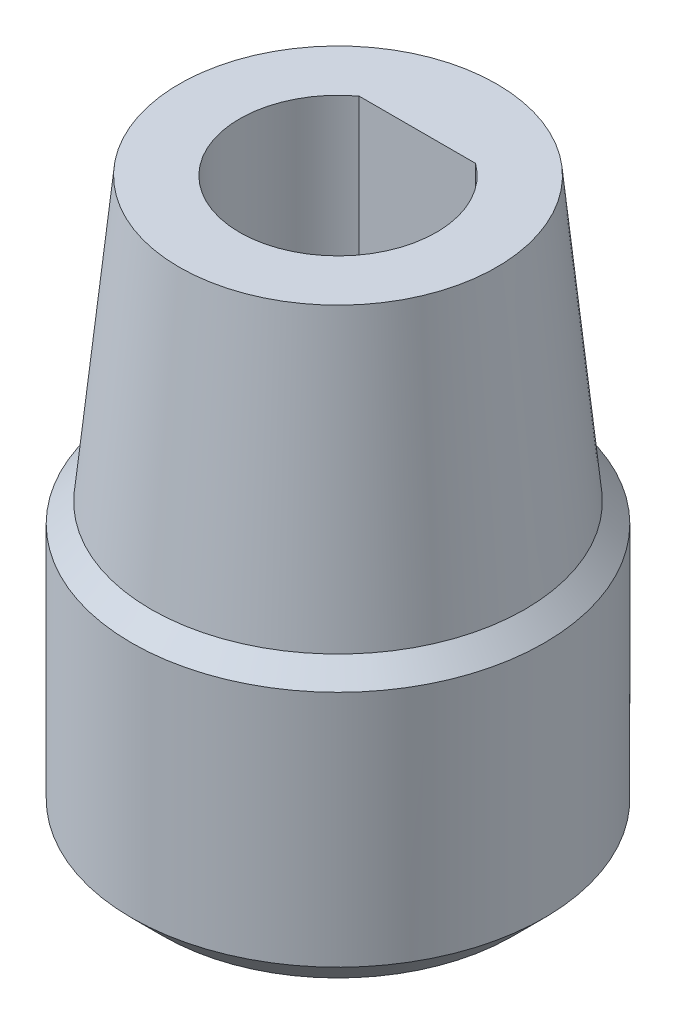
SolidWorks part; units mm, degrees
ref_plane "Front Plane" through (0, 0, 0) normal (0, 0, 1) x (1, 0, 0)
ref_plane "Top Plane" through (0, 0, 0) normal (0, 1, 0) x (1, 0, 0)
ref_plane "Right Plane" through (0, 0, 0) normal (1, 0, 0) x (0, 0, -1)
sketch "Sketch1" plane through (0, 0, 0) normal (0, 1, 0) x (1, 0, 0)
  line L0 (-1.833, 2.5) -> (1.833, 2.5)
  circle A0 centre (0, 0) radius 4.9
  circle A1 centre (0, 0) radius 3.1
  circle A2 centre (0, 0) radius 6
  circle A3 centre (0, 0) radius 6.5
  dimension "D1" = 9.8
  dimension "D2" = 6.2
  dimension "D4" = 12
  dimension "D5" = 13
  dimension "D3" = 2.5
extrude "Boss-Extrude1" add sketch "Sketch1" along normal blind 10 contours A2 A1 | L0 A1 | A2 A0 region at (0, 0, -2.7421) region at (-4.7614, 0, 0) region at (-5.8303, 0, 0)
extrude "Boss-Extrude2" add sketch "Sketch1<3>" along normal blind 3 contours A2 A1 | A1 region at (-4.7614, 0, 0)
sketch "Sketch1<3>" plane through (0, 0, 0) normal (0, 1, 0) x (1, 0, 0) same geometry as "Sketch1"
extrude "Boss-Extrude3" add sketch "Sketch1<6>" against normal blind 8 contours A3 A0 | A2 A0 region at (-5.8303, 0, 0) region at (-6.3162, 0, 0)
sketch "Sketch1<6>" plane through (0, 0, 0) normal (0, 1, 0) x (1, 0, 0) same geometry as "Sketch1"
chamfer "Chamfer1" distance 1 distance2 1 1 edges at (0, 0, 6)
chamfer "Chamfer2" distance 10 distance2 1 1 edges at (0, 10, 6) first distance on face at (0, 1, 6)
chamfer "Chamfer3" distance 1 angle 45 1 edges at (0, -8, 6.5)
